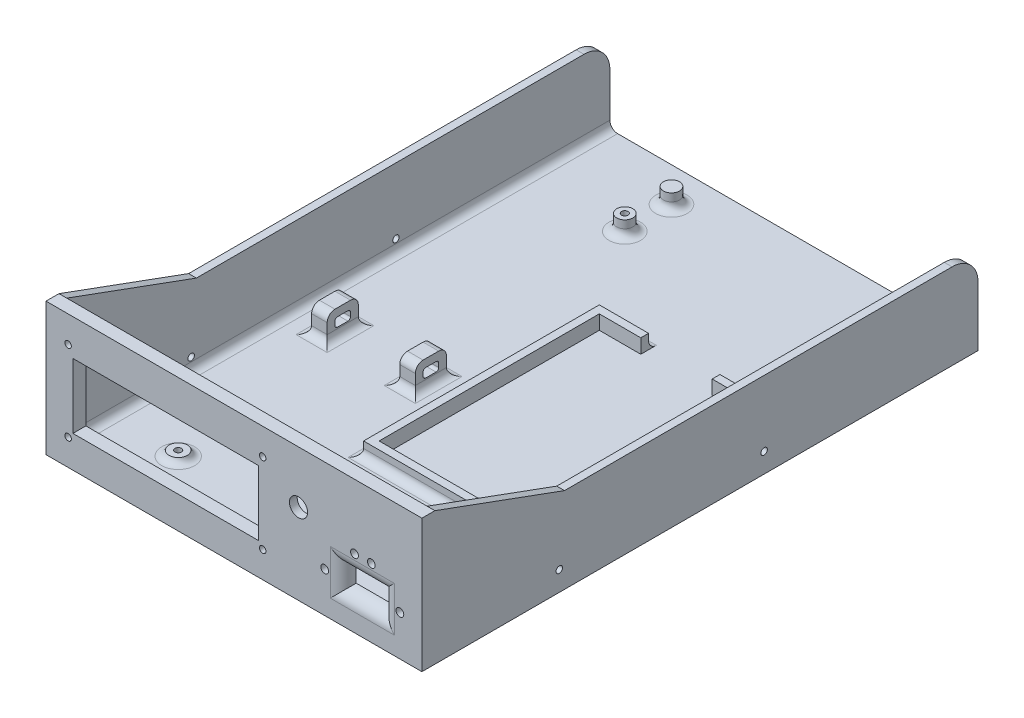
SolidWorks part; units mm, degrees
ref_plane "Front Plane" through (0, 0, 0) normal (0, 0, 1) x (1, 0, 0)
ref_plane "Top Plane" through (0, 0, 0) normal (0, 1, 0) x (1, 0, 0)
ref_plane "Right Plane" through (0, 0, 0) normal (1, 0, 0) x (0, 0, -1)
sketch "Sketch1" plane through (0, 0, 0) normal (0, 1, 0) x (1, 0, 0)
  line L1 (-105.3889, 49.1771) -> (39.6111, 49.1771)
  line L2 (-105.3889, 49.1771) -> (-105.3889, -165.3229)
  line L3 (-105.3889, -165.3229) -> (39.6111, -165.3229)
  line L4 (39.6111, 49.1771) -> (39.6111, -165.3229)
  dimension "D1" = 214.5
  dimension "D2" = 145
extrude "Boss-Extrude1" add sketch "Sketch1" along normal blind 3
sketch "Sketch3" plane through (0, 3, 0) normal (0, 1, 0) x (1, 0, 0)
  line L0 (-105.3889, 49.1771) -> (-105.3889, -165.3229) construction
  line L1 (-105.3889, -160.3229) -> (39.6111, -160.3229)
  line L2 (-105.3889, -160.3229) -> (-105.3889, -165.3229)
  line L3 (-105.3889, -165.3229) -> (39.6111, -165.3229)
  line L4 (39.6111, -160.3229) -> (39.6111, -165.3229)
  line L5 (39.6111, -165.3229) -> (39.6111, 49.1771) construction
  line L6 (-105.3889, -165.3229) -> (39.6111, -165.3229) construction
  dimension "D1" = 5
extrude "Boss-Extrude2" add sketch "Sketch3" along normal blind 48.3
sketch "Sketch4" plane through (0, 3, 0) normal (0, 1, 0) x (1, 0, 0)
  line L0 (39.6111, -160.3229) -> (-105.3889, -160.3229) construction
  line L1 (-102.3889, 49.1771) -> (-105.3889, 49.1771)
  line L2 (-102.3889, 49.1771) -> (-102.3889, -160.3229)
  line L3 (-102.3889, -160.3229) -> (-105.3889, -160.3229)
  line L4 (-105.3889, 49.1771) -> (-105.3889, -160.3229)
  line L5 (36.6111, 49.1771) -> (39.6111, 49.1771)
  line L6 (36.6111, 49.1771) -> (36.6111, -160.3229)
  line L7 (36.6111, -160.3229) -> (39.6111, -160.3229)
  line L8 (39.6111, 49.1771) -> (39.6111, -160.3229)
  line L9 (39.6111, -160.3229) -> (-105.3889, -160.3229) construction
  line L10 (39.6111, 49.1771) -> (-105.3889, 49.1771) construction
  line L11 (-105.3889, 49.1771) -> (-105.3889, -160.3229) construction
  line L12 (39.6111, -160.3229) -> (39.6111, 49.1771) construction
  dimension "D1" = 3
  dimension "D2" = 3
extrude "Boss-Extrude3" add sketch "Sketch4" along normal blind 30
sketch "Sketch5" plane through (-105.3889, 0, 0) normal (-1, 0, 0) x (0, 0, 1)
  line L0 (-49.1771, 0) -> (165.3229, 0) construction
  line L1 (165.3229, 51.3) -> (165.3229, 0) construction
  circle A0 centre (112.3229, 7.61) radius 1.25
  circle A1 centre (33.3229, 7.61) radius 1.25
  dimension "D3" = 2.5
  dimension "D4" = 2.5
  dimension "D1" = 79
  dimension "D2" = 7.61
  dimension "D5" = 53
extrude "Cut-Extrude1" cut sketch "Sketch5" against normal through all
sketch "Sketch6" plane through (0, 3, 0) normal (0, 1, 0) x (1, 0, 0)
  line L0 (39.6111, -160.3229) -> (39.6111, 49.1771) construction
  circle A0 centre (29.6111, 17.9387) radius 3.1
  circle A1 centre (-65.3889, 17.9387) radius 3.1
  circle A2 centre (-65.3889, 35.9387) radius 3.1
  circle A3 centre (29.6111, 35.9387) radius 3.1
  circle A4 centre (29.6111, 17.9387) radius 1.25
  circle A5 centre (-65.3889, 17.9387) radius 1.25
  dimension "D1" = 6.2
  dimension "D2" = 6.2
  dimension "D3" = 6.2
  dimension "D4" = 6.2
  dimension "D8" = 2.5
  dimension "D9" = 2.5
  dimension "D5" = 95
  dimension "D6" = 18
  dimension "D7" = 10
extrude "Boss-Extrude4" add sketch "Sketch6" along normal blind 6
sketch "Sketch7" plane through (0, 0, 165.3229) normal (0, 0, 1) x (1, 0, 0)
  line L1 (-95.0077, 37.3493) -> (-23.4477, 37.3493)
  line L2 (-95.0077, 37.3493) -> (-95.0077, 12.2993)
  line L3 (-95.0077, 12.2993) -> (-23.4477, 12.2993)
  line L4 (-23.4477, 37.3493) -> (-23.4477, 12.2993)
  line L5 (-99.9277, 43.4893) -> (-19.4677, 43.4893)
  line L6 (-99.9277, 43.4893) -> (-99.9277, 7.4093)
  line L7 (-99.9277, 7.4093) -> (-19.4677, 7.4093)
  line L8 (-19.4677, 43.4893) -> (-19.4677, 7.4093)
  circle A0 centre (-96.8677, 41.0793) radius 1.25
  circle A1 centre (-21.7977, 41.0793) radius 1.25
  circle A2 centre (-21.7977, 10.1093) radius 1.25
  circle A3 centre (-96.8677, 10.1093) radius 1.25
  dimension "D3" = 2.5
  dimension "D4" = 2.5
  dimension "D5" = 2.5
  dimension "D6" = 2.5
  dimension "D10" = 6.14
  dimension "D2" = 3.98
  dimension "D7" = 75.07
  dimension "D8" = 30.97
  dimension "D9" = 4.89
  dimension "D11" = 36.08
  dimension "D12" = 80.46
  dimension "D13" = 2.33
  dimension "D14" = 2.41
  dimension "D15" = 4.92
extrude "Cut-Extrude2" cut sketch "Sketch7" against normal up to next contours A0 | A3 | L4 L1 L2 L3 | A1 | A2 region at (-59.2277, 24.8243, 165.3229) region at (-96.8677, 41.0793, 165.3229) region at (-21.7977, 41.0793, 165.3229) region at (-21.7977, 10.1093, 165.3229) region at (-96.8677, 10.1093, 165.3229)
sketch "Sketch8" plane through (0, 0, 160.3229) normal (0, 0, -1) x (-1, 0, 0)
  line L1 (1.3607, 38.1212) -> (14.6207, 38.1212)
  line L2 (1.3607, 38.1212) -> (1.3607, 24.1312)
  line L3 (1.3607, 24.1312) -> (14.6207, 24.1312)
  line L4 (14.6207, 38.1212) -> (14.6207, 24.1312)
  circle A0 centre (7.9907, 31.1262) radius 3.5
  dimension "D3" = 7
  dimension "D1" = 13.26
  dimension "D2" = 13.99
  dimension "D4" = 6.63
  dimension "D5" = 6.995
extrude "Cut-Extrude3" cut sketch "Sketch8" against normal blind 2 contours L1 L4 L3 L2
extrude "Cut-Extrude4" cut sketch "Sketch8<3>" against normal up to next contours A0 region at (-7.9907, 31.1262, 160.3229)
sketch "Sketch8<3>" plane through (0, 0, 160.3229) normal (0, 0, -1) x (-1, 0, 0) same geometry as "Sketch8"
sketch "Sketch10" plane through (0, 0, 160.3229) normal (0, 0, -1) x (-1, 0, 0)
  line L0 (-39.6111, 51.3) -> (-39.6111, 0) construction
  circle A0 centre (-20.1111, 26.3994) radius 1.5
  circle A1 centre (-13.6111, 26.3994) radius 1.5
  dimension "D1" = 3
  dimension "D2" = 3
  dimension "D3" = 6.5
  dimension "D4" = 19.5
extrude "Cut-Extrude5" cut sketch "Sketch10" against normal through all
sketch "Sketch11" plane through (0, 3, 0) normal (0, 1, 0) x (1, 0, 0)
  line L0 (-102.3889, -160.3229) -> (-102.3889, 49.1771) construction
  line L1 (36.6111, -160.3229) -> (-102.3889, -160.3229) construction
  circle A0 centre (-76.3889, -143.3229) radius 1.25
  circle A1 centre (-76.3889, -122.1729) radius 1.25
  circle A2 centre (-76.3889, -143.3229) radius 3.5
  circle A3 centre (-76.3889, -122.1729) radius 3.5
  dimension "D2" = 2.5
  dimension "D3" = 2.5
  dimension "D4" = 7
  dimension "D5" = 7
  dimension "D1" = 21.15
  dimension "D6" = 26
  dimension "D7" = 17
extrude "Boss-Extrude5" add sketch "Sketch11" along normal blind 2
sketch "Sketch12" plane through (0, 3, 0) normal (0, 1, 0) x (1, 0, 0)
  line L1 (-85.2688, -76.9843) -> (-91.2688, -76.9843)
  line L2 (-85.2688, -76.9843) -> (-85.2688, -64.9843)
  line L3 (-85.2688, -64.9843) -> (-91.2688, -64.9843)
  line L4 (-91.2688, -76.9843) -> (-91.2688, -64.9843)
  line L5 (-57.2688, -76.9843) -> (-51.2688, -76.9843)
  line L6 (-57.2688, -76.9843) -> (-57.2688, -64.9843)
  line L7 (-57.2688, -64.9843) -> (-51.2688, -64.9843)
  line L8 (-51.2688, -76.9843) -> (-51.2688, -64.9843)
  dimension "D1" = 6
  dimension "D2" = 6
  dimension "D3" = 28
  dimension "D4" = 12
extrude "Boss-Extrude6" add sketch "Sketch12" along normal blind 10
sketch "Sketch13" plane through (-51.2688, 0, 0) normal (1, 0, 0) x (0, 0, -1)
  line L0 (-76.9843, 13) -> (-76.9843, 3) construction
  line L1 (-72.9843, 10) -> (-68.9843, 10)
  line L2 (-73.9843, 9) -> (-73.9843, 7.5)
  line L3 (-72.9843, 6.5) -> (-68.9843, 6.5)
  line L4 (-67.9843, 9) -> (-67.9843, 7.5)
  line L5 (-64.9843, 13) -> (-64.9843, 3) construction
  line L6 (-76.9843, 13) -> (-64.9843, 13) construction
  arc A0 (-67.9843, 9) -> (-68.9843, 10) centre (-68.9843, 9) ccw
  arc A1 (-68.9843, 6.5) -> (-67.9843, 7.5) centre (-68.9843, 7.5) ccw
  arc A2 (-73.9843, 7.5) -> (-72.9843, 6.5) centre (-72.9843, 7.5) ccw
  arc A3 (-72.9843, 10) -> (-73.9843, 9) centre (-72.9843, 9) ccw
  point P12 (-67.9843, 10)
  point P15 (-67.9843, 6.5)
  dimension "D5" = 1
  dimension "D6" = 1
  dimension "D7" = 1
  dimension "D8" = 1
  dimension "D1" = 3
  dimension "D2" = 3
  dimension "D3" = 3.5
  dimension "D4" = 3
extrude "Cut-Extrude6" cut sketch "Sketch13" against normal up to surface (40 mm away) up to face at (-91.2688, 8, 70.9843)
sketch "Sketch14" plane through (0, 3, 0) normal (0, 1, 0) x (1, 0, 0)
  line L0 (21.8066, -107.9913) -> (-40.2234, -107.9913)
  line L1 (18.8066, -104.9913) -> (-37.2234, -104.9913)
  line L2 (18.8066, -104.9913) -> (18.8066, -20.0613)
  line L3 (18.8066, -20.0613) -> (-37.2234, -20.0613)
  line L4 (-37.2234, -104.9913) -> (-37.2234, -20.0613)
  line L5 (-40.2234, -107.9913) -> (-40.2234, -17.0613)
  line L6 (21.8066, -17.0613) -> (-40.2234, -17.0613)
  line L7 (21.8066, -107.9913) -> (21.8066, -17.0613)
  circle A0 centre (29.6111, 17.9387) radius 1.25 construction
  dimension "D1" = 56.03
  dimension "D2" = 84.93
  dimension "D3" = 3
  dimension "D4" = 35
extrude "Boss-Extrude7" add sketch "Sketch14" along normal blind 5.5
sketch "Sketch15" plane through (0, 0, 17.0613) normal (0, 0, -1) x (-1, 0, 0)
  line L0 (-21.8066, 8.5) -> (40.2234, 8.5) construction
  line L1 (-6.3066, 8.5) -> (21.2234, 8.5)
  line L2 (-6.3066, 8.5) -> (-6.3066, 3)
  line L3 (-6.3066, 3) -> (21.2234, 3)
  line L4 (21.2234, 8.5) -> (21.2234, 3)
  line L5 (-21.8066, 3) -> (40.2234, 3) construction
  line L6 (-21.8066, 8.5) -> (-21.8066, 3) construction
  line L7 (40.2234, 8.5) -> (40.2234, 3) construction
  dimension "D1" = 15.5
  dimension "D2" = 19
extrude "Cut-Extrude7" cut sketch "Sketch15" against normal up to next
sketch "Sketch16" plane through (0, 0, 160.3229) normal (0, 0, -1) x (-1, 0, 0)
  line L0 (-36.6111, 33) -> (-36.6111, 3) construction
  line L1 (-23.9611, 19.1989) -> (-9.2611, 19.1989)
  line L2 (-23.9611, 19.1989) -> (-23.9611, 11.8989)
  line L3 (-23.9611, 11.8989) -> (-9.2611, 11.8989)
  line L4 (-9.2611, 19.1989) -> (-9.2611, 11.8989)
  circle A0 centre (-31.1111, 15.5489) radius 1.5
  circle A1 centre (-2.1111, 15.5489) radius 1.5
  dimension "D1" = 3
  dimension "D2" = 3
  dimension "D8" = 5.5
  dimension "D3" = 29
  dimension "D4" = 14.7
  dimension "D5" = 7.3
  dimension "D6" = 3.65
  dimension "D7" = 7.15
extrude "Cut-Extrude8" cut sketch "Sketch16" against normal up to next
extrude "Cut-Extrude9" cut sketch "Sketch6<2>" against normal up to next contours A5 | A4 region at (29.6111, 3, -17.9387) region at (-65.3889, 3, -17.9387)
sketch "Sketch6<2>" plane through (0, 3, 0) normal (0, 1, 0) x (1, 0, 0) same geometry as "Sketch6"
extrude "Cut-Extrude10" cut sketch "Sketch11<2>" against normal up to next contours A0 | A1 region at (-76.3889, 3, 143.3229) region at (-76.3889, 3, 122.1729)
sketch "Sketch11<2>" plane through (0, 3, 0) normal (0, 1, 0) x (1, 0, 0) same geometry as "Sketch11"
fillet "Fillet1" radius 5 4 edges at (23.9611, 15.5489, 165.3229) (16.6111, 11.8989, 165.3229) (9.2611, 15.5489, 165.3229) (16.6111, 19.1989, 165.3229)
fillet "Fillet2" radius 10 1 edges at (38.1111, 33, -49.1771)
fillet "Fillet3" radius 10 1 edges at (-103.8889, 33, -49.1771)
sketch "Sketch17" plane through (39.6111, 0, 0) normal (1, 0, 0) x (0, 0, -1)
  line L0 (-160.3229, 51.3) -> (-110.3229, 33)
  line L1 (-160.3229, 33) -> (39.1771, 33) construction
  line L2 (-110.3229, 33) -> (-160.3229, 33)
  line L3 (-160.3229, 33) -> (-160.3229, 51.3)
  dimension "D1" = 50
extrude "Boss-Extrude8" add sketch "Sketch17" against normal up to surface (3 mm away) up to face at (36.6111, 7.61, 111.0729)
sketch "Sketch18" plane through (-105.3889, 0, 0) normal (-1, 0, 0) x (0, 0, 1)
  line L0 (160.3229, 51.3) -> (110.3229, 33)
  line L1 (-39.1771, 33) -> (160.3229, 33) construction
  line L2 (110.3229, 33) -> (160.3229, 33)
  line L3 (160.3229, 33) -> (160.3229, 51.3)
  dimension "D1" = 50
extrude "Boss-Extrude9" add sketch "Sketch18" against normal up to surface (3 mm away) up to face at (-102.3889, 7.61, 113.5729)
fillet "Fillet4" radius 3 12 edges at (-54.2688, 3, 64.9843) (-51.2688, 3, 70.9843) (-57.2688, 3, 70.9843) (-54.2688, 3, 76.9843) (-88.2688, 3, 76.9843) (-91.2688, 3, 70.9843) (-88.2688, 3, 64.9843) (-85.2688, 3, 70.9843) (-88.2688, 13, 76.9843) (-88.2688, 13, 64.9843) (-54.2688, 13, 64.9843) (-54.2688, 13, 76.9843)
fillet "Fillet5" radius 3 5 edges at (14.0566, 3, 17.0613) (21.8066, 3, 62.5263) (-9.2084, 3, 107.9913) (-40.2234, 3, 62.5263) (-30.7234, 3, 17.0613)
fillet "Fillet6" radius 3 6 edges at (29.6111, 3, -32.8387) (29.6111, 3, -14.8387) (-65.3889, 3, -32.8387) (-65.3889, 3, -14.8387) (-76.3889, 3, 146.8229) (-76.3889, 3, 125.6729)
fillet "Fillet7" radius 3 3 edges at (36.6111, 3, 55.5729) (-102.3889, 3, 55.5729) (-32.8889, 3, 160.3229)
